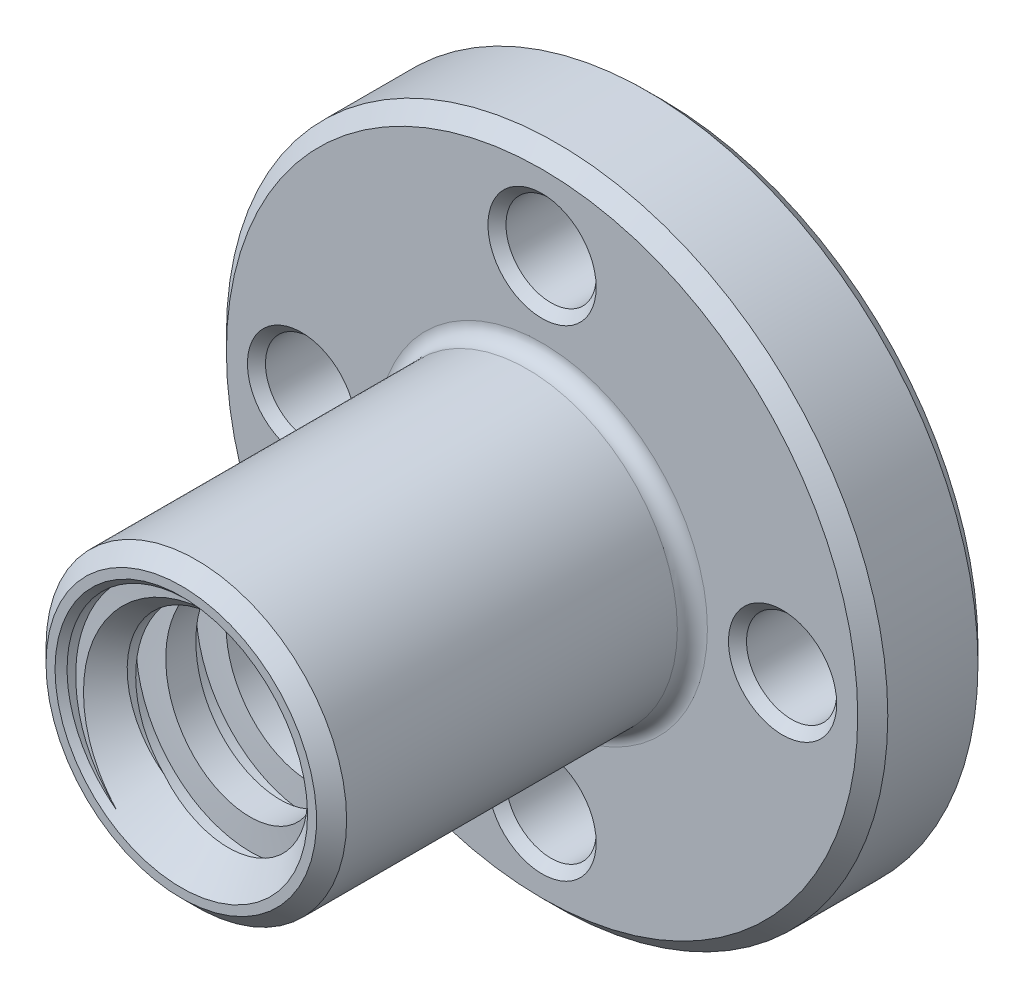
SolidWorks part; units mm, degrees
other "Камера1"
other "Камера2"
ref_plane "Спереди" through (0, 0, 0) normal (0, 0, 1) x (1, 0, 0)
ref_plane "Сверху" through (0, 0, 0) normal (0, 1, 0) x (1, 0, 0)
ref_plane "Справа" through (0, 0, 0) normal (1, 0, 0) x (0, 0, -1)
sketch "Эскиз1" plane through (0, 0, 0) normal (0, 0, 1) x (1, 0, 0)
  circle A0 centre (0, 0) radius 11
  dimension "D1" = 22
extrude "Бобышка-Вытянуть1" add sketch "Эскиз1" along normal blind 4
sketch "Эскиз2" plane through (0, 0, 0) normal (0, 0, -1) x (-1, 0, 0)
  circle A0 centre (0, 0) radius 5
  dimension "D1" = 10
extrude "Бобышка-Вытянуть2" add sketch "Эскиз2" along normal blind 2 and the other way blind 16
sketch "Эскиз3" plane through (0, 0, 16) normal (0, 0, 1) x (1, 0, 0)
  circle A0 centre (0, 0) radius 3
  dimension "D1" = 6
extrude "Вырез-Вытянуть1" cut sketch "Эскиз3" against normal through all
chamfer "Фаска1" distance 0.5 angle 45 4 edges at (-5, 0, -2) (-5, 0, 16) (11, 0, 0) (11, 0, 4)
fillet "Скругление1" radius 0.5 2 edges at (5, 0, 0) (5, 0, 4)
chamfer "Фаска2" distance 1.2 angle 45 2 edges at (3, 0, -2) (3, 0, 16)
ref_plane "Плоскость1" through (0, 0, 18) normal (0, 0, 1) x (1, 0, 0)
sketch "Эскиз4" plane through (0, 0, 18) normal (0, 0, 1) x (1, 0, 0)
  circle A0 centre (0, 0) radius 3 construction
  circle A1 centre (0, 0) radius 3
curve "Спираль1" pitch 2 height 22 radius 3 centre (0, 0, 18) axis (0, 0, -1) start towards (-1, 0, 0)
sketch "Эскиз6" plane through (0, 0, 0) normal (0, 1, 0) x (1, 0, 0)
  line L1 (-4, -17.5) -> (-3, -17.5)
  line L2 (-4, -17.5) -> (-4, -18.5)
  line L3 (-4, -18.5) -> (-3, -18.5)
  line L4 (-3, -17.5) -> (-3, -18.5)
  point P4 (-3, -18)
  dimension "D1" = 1
sweep "Вырез-По траектории1" cut profiles "Эскиз6" path "Спираль1" align with end faces yes
sketch "Эскиз7" plane through (0, 0, 4) normal (0, 0, 1) x (1, 0, 0)
  circle A0 centre (0, 8) radius 1.5
  circle A1 centre (8, 0) radius 1.5
  circle A2 centre (0, -8) radius 1.5
  circle A3 centre (-8, 0) radius 1.5
  point P12 (0, 0)
  dimension "D1" = 3
  dimension "D2" = 8
  dimension "D3" = 4
extrude "Вырез-Вытянуть2" cut sketch "Эскиз7" against normal through all
chamfer "Фаска3" distance 0.3 angle 45 8 edges at (9.5, 0, 4) (9.5, 0, 0) (1.5, -8, 4) (1.5, -8, 0) (-6.5, 0, 4) (-6.5, 0, 0) (1.5, 8, 0) (1.5, 8, 4)
